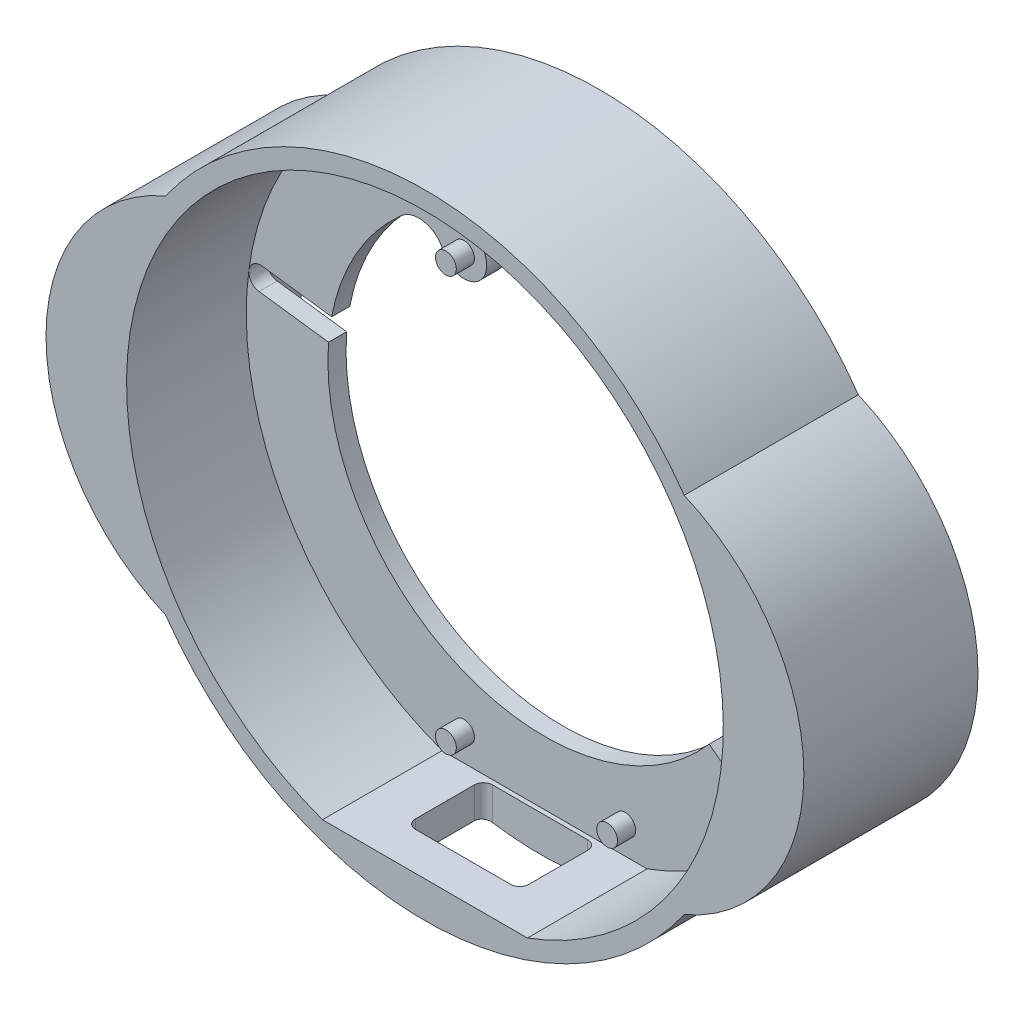
SolidWorks part; units mm, degrees
ref_plane "Plan de face" through (0, 0, 0) normal (0, 0, 1) x (1, 0, 0)
ref_plane "Plan de dessus" through (0, 0, 0) normal (0, 1, 0) x (1, 0, 0)
ref_plane "Plan de droite" through (0, 0, 0) normal (1, 0, 0) x (0, 0, -1)
sketch "Esquisse_carte_affichage" plane through (0, 0, 0) normal (0, 0, 1) x (1, 0, 0)
  circle A0 centre (19.25, 25.1) radius 0.5
  circle A1 centre (25.07, -19.23) radius 0.5
  circle A2 centre (29.18, 12.09) radius 0.5
  circle A3 centre (31.32, -4.14) radius 0.5
  circle A4 centre (-29.21, -12.07) radius 0.5
  circle A5 centre (-31.32, 4.14) radius 0.5
  circle A6 centre (-26.4935, -7.4094) radius 0.25
  circle A7 centre (-23.6728, -14.0139) radius 0.25
  circle A8 centre (-19.2392, -19.6637) radius 0.25
  circle A9 centre (-13.4943, -23.973) radius 0.25
  circle A10 centre (-6.8298, -26.6487) radius 0.25
  circle A11 centre (0.3, -27.5085) radius 0.25
  circle A12 centre (7.4094, -26.4935) radius 0.25
  circle A13 centre (14.0139, -23.6728) radius 0.25
  circle A14 centre (19.6637, -19.2392) radius 0.25
  circle A15 centre (23.973, -13.4943) radius 0.25
  circle A16 centre (26.6487, -6.8298) radius 0.25
  circle A17 centre (27.5085, 0.3) radius 0.25
  circle A18 centre (26.4935, 7.4094) radius 0.25
  circle A19 centre (23.6728, 14.0139) radius 0.25
  circle A20 centre (19.2392, 19.6637) radius 0.25
  circle A21 centre (13.4943, 23.973) radius 0.25
  circle A22 centre (6.8298, 26.6487) radius 0.25
  circle A23 centre (-0.3, 27.5085) radius 0.25
  circle A24 centre (-7.4094, 26.4935) radius 0.25
  circle A25 centre (-14.0139, 23.6728) radius 0.25
  circle A26 centre (-19.6637, 19.2392) radius 0.25
  circle A27 centre (-23.973, 13.4943) radius 0.25
  circle A28 centre (-26.6487, 6.8298) radius 0.25
  circle A29 centre (-27.5085, -0.3) radius 0.25
  circle A30 centre (-30.2, -7.1) radius 0.25
  circle A31 centre (-26.5986, -15.746) radius 0.25
  circle A32 centre (-28.1305, -7.8674) radius 0.25
  circle A33 centre (-21.6169, -22.0937) radius 0.25
  circle A34 centre (-25.1358, -14.8801) radius 0.25
  circle A35 centre (-15.162, -26.9359) radius 0.25
  circle A36 centre (-20.428, -20.8785) radius 0.25
  circle A37 centre (-7.6738, -29.9423) radius 0.25
  circle A38 centre (-14.3281, -25.4544) radius 0.25
  circle A39 centre (0.3371, -30.9082) radius 0.25
  circle A40 centre (-7.252, -28.2956) radius 0.25
  circle A41 centre (8.3254, -29.7678) radius 0.25
  circle A42 centre (0.3185, -29.2082) radius 0.25
  circle A43 centre (15.746, -26.5986) radius 0.25
  circle A44 centre (7.8674, -28.1305) radius 0.25
  circle A45 centre (22.0937, -21.6169) radius 0.25
  circle A46 centre (14.8801, -25.1358) radius 0.25
  circle A47 centre (26.9359, -15.162) radius 0.25
  circle A48 centre (20.8785, -20.428) radius 0.25
  circle A49 centre (29.9423, -7.6738) radius 0.25
  circle A50 centre (25.4544, -14.3281) radius 0.25
  circle A51 centre (30.9082, 0.3371) radius 0.25
  circle A52 centre (28.2956, -7.252) radius 0.25
  circle A53 centre (29.7678, 8.3254) radius 0.25
  circle A54 centre (29.2082, 0.3185) radius 0.25
  circle A55 centre (26.5986, 15.746) radius 0.25
  circle A56 centre (28.1305, 7.8674) radius 0.25
  circle A57 centre (21.6169, 22.0937) radius 0.25
  circle A58 centre (25.1358, 14.8801) radius 0.25
  circle A59 centre (15.162, 26.9359) radius 0.25
  circle A60 centre (20.428, 20.8785) radius 0.25
  circle A61 centre (7.6738, 29.9423) radius 0.25
  circle A62 centre (14.3281, 25.4544) radius 0.25
  circle A63 centre (-0.3371, 30.9082) radius 0.25
  circle A64 centre (7.252, 28.2956) radius 0.25
  circle A65 centre (-8.3254, 29.7678) radius 0.25
  circle A66 centre (-0.3185, 29.2082) radius 0.25
  circle A67 centre (-15.746, 26.5986) radius 0.25
  circle A68 centre (-7.8674, 28.1305) radius 0.25
  circle A69 centre (-22.0937, 21.6169) radius 0.25
  circle A70 centre (-14.8801, 25.1358) radius 0.25
  circle A71 centre (-26.9359, 15.162) radius 0.25
  circle A72 centre (-20.8785, 20.428) radius 0.25
  circle A73 centre (-29.9423, 7.6738) radius 0.25
  circle A74 centre (-25.4544, 14.3281) radius 0.25
  circle A75 centre (-30.9082, -0.3371) radius 0.25
  circle A76 centre (-28.2956, 7.252) radius 0.25
  circle A77 centre (0, 0) radius 26.162
  circle A78 centre (0, 0) radius 32.766
  dimension "D1" = 65.532
  dimension "D2" = 52.324
sketch "Esquisse_carte_mère" plane through (0, 0, 0) normal (0, 0, 1) x (1, 0, 0)
  line L0 (-11.3435, -28.5174) -> (-11.0897, -29.13)
  line L1 (-11.0897, -29.13) -> (-10.6861, -29.6561)
  line L2 (-10.6861, -29.6561) -> (-10.16, -30.0597)
  line L3 (-10.16, -30.0597) -> (-9.5474, -30.3135)
  line L4 (-9.5474, -30.3135) -> (-8.89, -30.4)
  line L5 (-8.89, -30.4) -> (-2.413, -30.4)
  line L6 (-2.413, -30.4) -> (-1.905, -29.892)
  line L7 (-1.905, -29.892) -> (1.905, -29.892)
  line L8 (1.905, -29.892) -> (2.413, -30.4)
  line L9 (2.413, -30.4) -> (8.89, -30.4)
  line L10 (8.89, -30.4) -> (9.5474, -30.3135)
  line L11 (9.5474, -30.3135) -> (10.16, -30.0597)
  line L12 (10.16, -30.0597) -> (10.6861, -29.6561)
  line L13 (10.6861, -29.6561) -> (11.0897, -29.13)
  line L14 (11.0897, -29.13) -> (11.3435, -28.5174)
  line L15 (11.3435, -28.5174) -> (11.43, -27.86)
  line L16 (11.43, -27.86) -> (11.43, 17.86)
  line L17 (11.43, 17.86) -> (11.3435, 18.5174)
  line L18 (11.3435, 18.5174) -> (11.0897, 19.13)
  line L19 (11.0897, 19.13) -> (10.6861, 19.6561)
  line L20 (10.6861, 19.6561) -> (10.16, 20.0597)
  line L21 (10.16, 20.0597) -> (9.5474, 20.3135)
  line L22 (9.5474, 20.3135) -> (8.89, 20.4)
  line L23 (8.89, 20.4) -> (-8.89, 20.4)
  line L24 (-8.89, 20.4) -> (-9.5474, 20.3135)
  line L25 (-9.5474, 20.3135) -> (-10.16, 20.0597)
  line L26 (-10.16, 20.0597) -> (-10.6861, 19.6561)
  line L27 (-10.6861, 19.6561) -> (-11.0897, 19.13)
  line L28 (-11.0897, 19.13) -> (-11.3435, 18.5174)
  line L29 (-11.3435, 18.5174) -> (-11.43, 17.86)
  line L30 (-11.43, 17.86) -> (-11.43, -27.86)
  line L31 (-11.43, -27.86) -> (-11.3435, -28.5174)
  line L32 (8.9522, -28.0199) -> (-18113.3609, 46572.2136) construction
  line L33 (-8.9266, -27.9541) -> (18113.3865, 46572.2795) construction
  circle A0 centre (-3.3, -25.05) radius 0.4
  circle A1 centre (3.3, -25.05) radius 0.4
  circle A2 centre (-3.6, -27.86) radius 0.45
  circle A3 centre (3.6, -27.86) radius 0.45
  circle A4 centre (10.16, 14.05) radius 0.5
  circle A5 centre (10.16, 11.51) radius 0.5
  circle A6 centre (10.16, 8.97) radius 0.5
  circle A7 centre (10.16, 6.43) radius 0.5
  circle A8 centre (10.16, 3.89) radius 0.5
  circle A9 centre (10.16, 1.35) radius 0.5
  circle A10 centre (10.16, -1.19) radius 0.5
  circle A11 centre (10.16, -3.73) radius 0.5
  circle A12 centre (10.16, -6.27) radius 0.5
  circle A13 centre (10.16, -8.81) radius 0.5
  circle A14 centre (10.16, -11.35) radius 0.5
  circle A15 centre (10.16, -13.89) radius 0.5
  circle A16 centre (-10.16, -24.05) radius 0.5
  circle A17 centre (-10.16, -21.51) radius 0.5
  circle A18 centre (-10.16, -18.97) radius 0.5
  circle A19 centre (-10.16, -16.43) radius 0.5
  circle A20 centre (-10.16, -13.89) radius 0.5
  circle A21 centre (-10.16, -11.35) radius 0.5
  circle A22 centre (-10.16, -8.81) radius 0.5
  circle A23 centre (-10.16, -6.27) radius 0.5
  circle A24 centre (-10.16, -3.73) radius 0.5
  circle A25 centre (-10.16, -1.19) radius 0.5
  circle A26 centre (-10.16, 1.35) radius 0.5
  circle A27 centre (-10.16, 3.89) radius 0.5
  circle A28 centre (-10.16, 6.43) radius 0.5
  circle A29 centre (-10.16, 8.97) radius 0.5
  circle A30 centre (-10.16, 11.51) radius 0.5
  circle A31 centre (-10.16, 14.05) radius 0.5
  circle A32 centre (-8.89, -27.86) radius 1.25
  circle A33 centre (8.89, -27.86) radius 1.25
  circle A34 centre (-8.89, 17.86) radius 1.25
  circle A35 centre (8.89, 17.86) radius 1.25
  circle A36 centre (-1.95, -25.955) radius 0.35
  circle A37 centre (1.95, -25.955) radius 0.35
  circle A38 centre (-2.2, 15.706) radius 0.45
  circle A39 centre (3.048, -15.795) radius 0.25
  circle A40 centre (1.016, -20.875) radius 0.25
  circle A41 centre (-6.223, -9.826) radius 0.25
  circle A42 centre (-6.096, -16.43) radius 0.25
  circle A43 centre (7.3914, -2.0028) radius 0.25
  circle A44 centre (7.366, -18.462) radius 0.25
  circle A45 centre (-1.905, 12.018) radius 0.25
  circle A46 centre (1.905, 9.224) radius 0.25
  circle A47 centre (-5.715, -21.129) radius 0.25
  circle A48 centre (-4.064, -1.571) radius 0.25
  circle A49 centre (-8.509, -22.78) radius 0.25
  circle A50 centre (0.2286, -14.5758) radius 0.25
  circle A51 centre (0.508, 7.446) radius 0.25
  circle A52 centre (0.635, 8.589) radius 0.25
  circle A53 centre (-7.112, 0.334) radius 0.25
  circle A54 centre (4.953, -15.795) radius 0.25
  circle A55 centre (0, 10.494) radius 0.25
  circle A56 centre (-4.191, -16.43) radius 0.25
  circle A57 centre (-0.889, -17.573) radius 0.25
  circle A58 centre (5.842, -10.715) radius 0.25
  circle A59 centre (2.159, -17.446) radius 0.25
  circle A60 centre (0, -27.987) radius 0.25
  circle A61 centre (-1.397, 4.271) radius 0.25
  circle A62 centre (-5.207, 1.985) radius 0.25
  circle A63 centre (-0.381, -6.651) radius 0.25
  circle A64 centre (6.858, 8.462) radius 0.25
  circle A65 centre (5.207, 3.128) radius 0.25
  circle A66 centre (2.667, 4.525) radius 0.25
  circle A67 centre (5.08, 11.764) radius 0.25
  circle A68 centre (0, 14.431) radius 0.25
  circle A69 centre (-1.778, 8.716) radius 0.25
  circle A70 centre (-2.921, 4.271) radius 0.25
  circle A71 centre (-5.588, 3.128) radius 0.25
  circle A72 centre (-1.905, -19.732) radius 0.25
  circle A73 centre (-5.842, -8.683) radius 0.25
  circle A74 centre (-3.048, -20.113) radius 0.25
  circle A75 centre (-6.604, -7.667) radius 0.25
  circle A76 centre (-5.207, -10.842) radius 0.25
  circle A77 centre (10.668, -26.082) radius 0.25
  circle A78 centre (5.969, -4.365) radius 0.25
  circle A79 centre (5.08, -9.191) radius 0.25
  circle A80 centre (-3.81, -3.349) radius 0.25
  circle A81 centre (-4.953, -9.699) radius 0.25
  circle A82 centre (3.048, 6.43) radius 0.25
  circle A83 centre (5.969, -3.222) radius 0.25
  circle A84 centre (6.858, -7.667) radius 0.25
  circle A85 centre (6.477, 6.303) radius 0.25
  circle A86 centre (-1.27, 10.367) radius 0.25
  circle A87 centre (-1.0922, -0.1994) radius 0.25
  circle A88 centre (0.508, -0.428) radius 0.25
  circle A89 centre (4.318, -17.065) radius 0.25
  circle A90 centre (1.524, 4.144) radius 0.25
  circle A91 centre (-2.921, -1.444) radius 0.25
  circle A92 centre (3.302, -10.08) radius 0.25
  circle A93 centre (-3.81, -10.08) radius 0.25
  circle A94 centre (-5.08, -6.778) radius 0.25
  point P222 (0, -5)
  dimension "D5" = 2.5
  dimension "D1" = 2.54
  dimension "D2" = 2.54
  dimension "D3" = 2.54
  dimension "D4" = 2.54
sketch "Esquisse_support" plane through (0, 0, 0) normal (0, 0, 1) x (1, 0, 0)
  line L0 (0, 0) -> (0, -50000) construction
  line L1 (0, 0) -> (-31.32, 4.14) construction
  line L2 (0, 0) -> (19.25, 25.1) construction
  line L3 (0, 0) -> (25.07, -19.23) construction
  line L4 (25.07, -19.23) -> (30456.2807, 39653.7005) construction
  line L5 (19.25, 25.1) -> (39694.4792, -30403.1136) construction
  line L6 (-31.32, 4.14) -> (6520.8813, 49572.9675) construction
  line L7 (-31.1487, 5.4363) -> (-23.4871, 4.4235)
  line L8 (-31.4913, 2.8437) -> (-23.8298, 1.831)
  line L9 (18.2437, 25.8718) -> (13.5179, 19.7098)
  line L10 (20.2563, 24.3282) -> (15.5305, 18.1663)
  line L11 (25.8637, -18.1952) -> (19.7291, -13.4897)
  line L12 (24.2763, -20.2648) -> (18.1417, -15.5592)
  line L13 (-8.89, 17.86) -> (46591.3436, 18140.1731) construction
  line L14 (8.89, 17.86) -> (-46591.3436, 18140.1731) construction
  line L15 (11.22, 16.9539) -> (13.5179, 19.7098)
  line L16 (72498.2044, -186428.9542) -> (-90602.6131, 232973.148) construction
  line L17 (-72498.1788, -186428.8884) -> (90602.6387, 232973.2138) construction
  circle A0 centre (0, 0) radius 32.9 construction
  circle A1 centre (0, 0) radius 34.9
  arc A2 (-32.6163, 4.3113) -> (-31.4913, 2.8437) centre (-31.32, 4.14) ccw
  arc A3 (-32.6163, 4.3113) -> (-31.1487, 5.4363) centre (-31.32, 4.14) cw
  arc A4 (20.0218, 26.1063) -> (18.2437, 25.8718) centre (19.25, 25.1) ccw
  arc A5 (20.0218, 26.1063) -> (20.2563, 24.3282) centre (19.25, 25.1) cw
  arc A6 (26.1048, -20.0237) -> (25.8637, -18.1952) centre (25.07, -19.23) ccw
  arc A7 (26.1048, -20.0237) -> (24.2763, -20.2648) centre (25.07, -19.23) cw
  arc A8 (-23.4871, 4.4235) -> (13.5179, 19.7098) centre (0, 0) cw construction
  arc A9 (-23.8298, 1.831) -> (18.1417, -15.5592) centre (0, 0) ccw
  arc A10 (19.7291, -13.4897) -> (15.5305, 18.1663) centre (0, 0) ccw
  arc A11 (-6.56, 18.7661) -> (-11.22, 16.9539) centre (-8.89, 17.86) cw
  arc A12 (6.56, 18.7661) -> (11.22, 16.9539) centre (8.89, 17.86) ccw
  arc A13 (-6.56, 18.7661) -> (-4.1838, 23.531) centre (-3.28, 20.1053) cw
  arc A14 (6.56, 18.7661) -> (4.1838, 23.531) centre (3.28, 20.1053) ccw
  arc A15 (-11.22, 16.9539) -> (-15.8818, 17.86) centre (-13.8724, 15.7529) ccw
  arc A16 (-23.4871, 4.4235) -> (-15.8818, 17.86) centre (0, 0) cw
  arc A17 (-4.1838, 23.531) -> (4.1838, 23.531) centre (0, 0) cw
  point P37 (-4.1838, 23.531)
  dimension "D1" = 65.8
  dimension "D2" = 69.8
  dimension "D12" = 2.5
  dimension "D13" = 2.5
  dimension "D3" = 90
  dimension "D4" = 90
  dimension "D5" = 90
  dimension "D7" = 90
  dimension "D8" = 90
  dimension "D9" = 90
  dimension "D10" = 90
  dimension "D11" = 90
extrude "Boss.-Extru.1" add sketch "Esquisse_support" along normal blind 2 contours A1 A13 A17 A14 A12 L15 L9 A4 A5 L10 A10 L11 A6 A7 L12 A9 L8 A2 A3 L7 A16 A15 A11 region at (-33.9129, 0, 0)
sketch "Esquisse6" plane through (0, 0, 2) normal (0, 0, 1) x (1, 0, 0)
  line L0 (0, 0) -> (0, -50000) construction
  circle A0 centre (-8.89, 17.86) radius 1.15
  circle A1 centre (-8.89, -27.86) radius 1.15
  circle A2 centre (8.89, -27.86) radius 1.15
  circle A3 centre (8.89, 17.86) radius 1.15
  dimension "D1" = 2.3
  dimension "D2" = 2.3
extrude "Boss.-Extru.2" add sketch "Esquisse6" along normal blind 2
sketch "Esquisse7" plane through (0, 0, 0) normal (0, 0, -1) x (-1, 0, 0)
  circle A0 centre (0, 0) radius 34.9
  circle A1 centre (0, 0) radius 32.9
extrude "Boss.-Extru.3" add sketch "Esquisse7" along normal blind 4
sketch "Esquisse8" plane through (0, 0, 2) normal (0, 0, 1) x (1, 0, 0)
  line L0 (0, 0) -> (0, -50000) construction
  line L1 (-11.296, -30.9) -> (11.296, -30.9)
  line L2 (-8.89, -30.4) -> (-2.413, -30.4) construction
  circle A0 centre (0, 0) radius 34.9
  circle A1 centre (0, 0) radius 32.9 construction
  arc A2 (-11.296, -30.9) -> (11.296, -30.9) centre (0, 0) cw
  point P9 (0, -30.9)
  circle M5 centre (0, 0) radius 34.9
  dimension "D2" = 0.5
extrude "Boss.-Extru.5" add sketch "Esquisse8" along normal blind 13.2 contours A2 L1 M5 region at (-33.9129, 0, 2)
sketch "Ouverture_USB" plane through (0, -30.9, 0) normal (0, 1, 0) x (1, 0, 0)
  line L0 (0, -16.2747) -> (0, 5.3613) construction
  line L2 (-5.25, -11) -> (5.25, -11)
  line L3 (-6.25, -10) -> (-6.25, -3.5)
  line L4 (-5.25, -2.5) -> (5.25, -2.5)
  line L5 (6.25, -10) -> (6.25, -3.5)
  arc A0 (6.25, -10) -> (5.25, -11) centre (5.25, -10) cw
  arc A1 (6.25, -3.5) -> (5.25, -2.5) centre (5.25, -3.5) ccw
  arc A2 (-5.25, -2.5) -> (-6.25, -3.5) centre (-5.25, -3.5) ccw
  arc A3 (-6.25, -10) -> (-5.25, -11) centre (-5.25, -10) ccw
  dimension "D4" = 1
  dimension "D1" = 8.5
  dimension "D2" = 12.5
  dimension "D3" = 2.5
extrude "Enlèv. mat.-Extru.1" cut sketch "Ouverture_USB" against normal blind 10
sketch "Esquisse10" plane through (0, 0, 15.2) normal (0, 0, 1) x (1, 0, 0)
  line L0 (0, 0) -> (0, -15.0414) construction
  line L1 (-34.9, 0) -> (0, 0) construction
  arc A0 (-28.5884, 20.0178) -> (-28.5884, -20.0178) centre (0, 0) ccw
  arc A1 (-28.5884, 20.0178) -> (-28.5884, -20.0178) centre (-20, 0) ccw
  circle A2 centre (0, 0) radius 34.9 construction
  arc A3 (28.5884, 20.0178) -> (28.5884, -20.0178) centre (0, 0) cw
  arc A4 (28.5884, 20.0178) -> (28.5884, -20.0178) centre (20, 0) cw
  point P4 (-34.9, 0)
  dimension "D1" = 20
extrude "Boss.-Extru.9" add sketch "Esquisse10" against normal through all
sketch "Esquisse11" plane through (0, 0, 0) normal (0, 1, 0) x (1, 0, 0)
  line L0 (-28.5884, 4) -> (-39.1082, -7.3219)
  line L1 (-41.7824, 4) -> (-41.7824, -15.2) construction
  line L2 (-200034.9, -15.2) -> (200000, -15.2) construction
  line L3 (-41.7824, -14.1287) -> (-41.7824, -15.2)
  line L4 (-41.7824, -15.2) -> (-28.5884, -15.2) construction
  line L5 (-41.7824, -15.2) -> (-40.7824, -15.2)
  arc A0 (-39.1082, -7.3219) -> (-41.7824, -14.1287) centre (-31.7824, -14.1287) ccw
  ellipse E0 centre (-35.1854, -15.2) end of major axis (-40.7824, -15.2) minor radius 2.7987 (-35.2202, -12.4014) -> (-40.7824, -15.2) ccw
  point P9 (-41.7824, -10.2)
  dimension "D2" = 10
  dimension "D1" = 5
  dimension "D3" = 1
